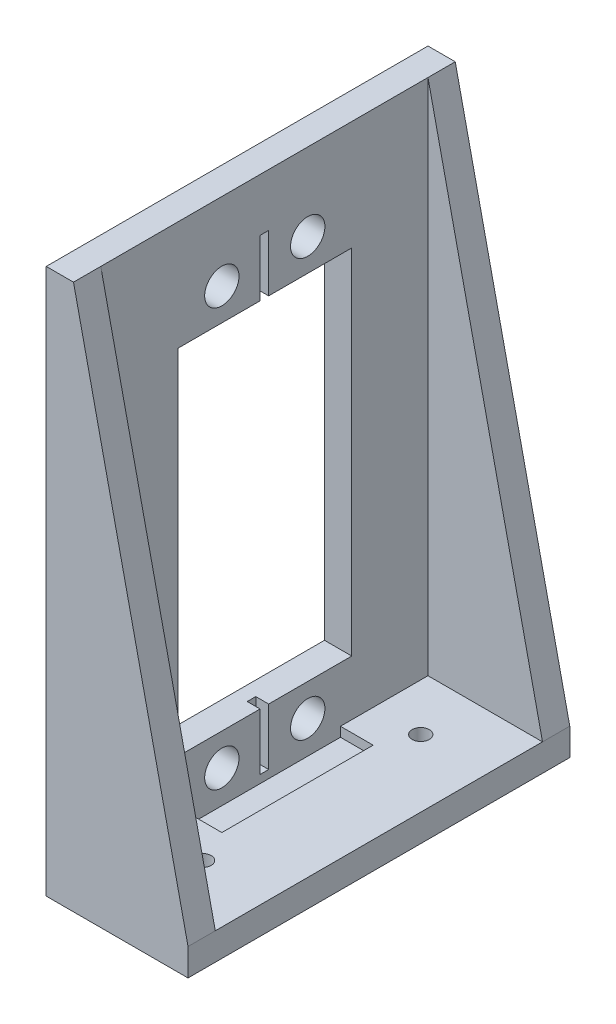
SolidWorks part; units mm, degrees
ref_plane "Front Plane" through (0, 0, 0) normal (0, 0, 1) x (1, 0, 0)
ref_plane "Top Plane" through (0, 0, 0) normal (0, 1, 0) x (1, 0, 0)
ref_plane "Right Plane" through (0, 0, 0) normal (1, 0, 0) x (0, 0, -1)
sketch "Sketch1" plane through (0, 0, 0) normal (0, 0, 1) x (1, 0, 0)
  line L0 (0, 0) -> (0, 63.5)
  line L1 (0, 63.5) -> (3.175, 63.5)
  line L2 (3.175, 63.5) -> (3.175, 3.175)
  line L3 (3.175, 3.175) -> (16.51, 3.175)
  line L4 (16.51, 3.175) -> (16.51, 0)
  line L5 (16.51, 0) -> (0, 0)
  dimension "D1" = 3.175
  dimension "D2" = 3.175
  dimension "D3" = 16.51
  dimension "D4" = 63.5
extrude "Boss-Extrude1" add sketch "Sketch1" along normal mid plane 44.45
sketch "Sketch3" plane through (0, 0, 22.225) normal (0, 0, 1) x (1, 0, 0)
  line L0 (3.175, 63.5) -> (16.51, 3.175)
  line L1 (16.51, 3.175) -> (3.175, 3.175)
  line L2 (3.175, 3.175) -> (3.175, 63.5)
extrude "Boss-Extrude2" add sketch "Sketch3" against normal blind 3.175
mirror "Mirror1" about plane through (0, 0, 0) normal (0, 0, 1) of "Boss-Extrude2"
sketch "Sketch4" plane through (0, 3.175, 0) normal (0, 1, 0) x (1, 0, 0)
  line L1 (3.175, 19.05) -> (16.51, 19.05) construction
  line L3 (3.175, 0) -> (16.51, 0) construction
  line L4 (3.175, -19.05) -> (3.175, 19.05) construction
  line L5 (16.51, -19.05) -> (16.51, 19.05) construction
  circle A0 centre (8.68, 12.7) radius 1
  circle A3 centre (8.68, -12.7) radius 1
  dimension "D1" = 2
  dimension "D2" = 6.35
  dimension "D3" = 5.505
extrude "Cut-Extrude2" cut sketch "Sketch4" against normal through all
sketch "Sketch5" plane through (3.175, 0, 0) normal (1, 0, 0) x (0, 0, -1)
  line L0 (-19.05, 63.5) -> (-19.05, 3.175) construction
  line L1 (-19.05, 3.175) -> (19.05, 3.175) construction
  circle A0 centre (-4.953, 5.875) radius 2
  circle A1 centre (5.047, 5.875) radius 2
  circle A2 centre (-4.953, 54.475) radius 2
  circle A3 centre (5.047, 54.475) radius 2
  dimension "D3" = 4
  dimension "D5" = 4
  dimension "D7" = 4
  dimension "D8" = 4
  dimension "D1" = 14.097
  dimension "D2" = 2.7
  dimension "D4" = 10
  dimension "D6" = 48.6
extrude "Cut-Extrude3" cut sketch "Sketch5" against normal through all
sketch "Sketch6" plane through (3.175, 0, 0) normal (1, 0, 0) x (0, 0, -1)
  line L0 (-10.08, 50.752) -> (10.174, 9.598) construction
  line L1 (-10.08, 50.752) -> (10.174, 50.752)
  line L2 (-10.08, 50.752) -> (-10.08, 9.598)
  line L3 (-10.08, 9.598) -> (10.174, 9.598)
  line L4 (10.174, 50.752) -> (10.174, 9.598)
  line L5 (10.174, 50.752) -> (-10.08, 9.598) construction
  line L6 (-4.953, 54.475) -> (5.047, 5.875) construction
  line L7 (-4.953, 5.875) -> (5.047, 54.475) construction
  point P12 (0.047, 30.175)
  point P13 (0.047, 30.175)
  dimension "D1" = 41.154
  dimension "D2" = 20.254
extrude "Cut-Extrude4" cut sketch "Sketch6" against normal through all
sketch "Sketch7" plane through (0, 50.752, 0) normal (0, -1, 0) x (1, 0, 0)
  line L0 (3.175, -10.174) -> (3.175, 10.08) construction
  line L1 (1.675, -0.5) -> (3.175, -0.5)
  line L2 (1.675, -0.5) -> (1.675, 0.5)
  line L3 (1.675, 0.5) -> (3.175, 0.5)
  line L4 (3.175, -0.5) -> (3.175, 0.5)
  line L5 (1.675, -0.5) -> (3.175, 0.5) construction
  line L6 (1.675, 0.5) -> (3.175, -0.5) construction
  line L7 (9.0805, 0) -> (-9.0805, 0) construction
  point P0 (2.425, 0)
  dimension "D1" = 1
  dimension "D2" = 1.5
extrude "Cut-Extrude5" cut sketch "Sketch7" against normal blind 6.604
extrude "Cut-Extrude6" cut sketch "Sketch7<2>" along normal blind 6.604 from surface starting at face at (1.5875, 9.598, -0.047)
sketch "Sketch7<2>" plane through (0, 50.752, 0) normal (0, -1, 0) x (1, 0, 0) same geometry as "Sketch7"
sketch "Sketch9" plane through (16.51, 0, 0) normal (1, 0, 0) x (0, 0, -1)
  line L1 (-8.763, 5.292) -> (8.857, 5.292)
  line L2 (-8.763, 5.292) -> (-8.763, 2.065)
  line L3 (-8.763, 2.065) -> (8.857, 2.065)
  line L4 (8.857, 5.292) -> (8.857, 2.065)
  circle A0 centre (5.047, 5.875) radius 2 construction
  circle A1 centre (-4.953, 5.875) radius 2 construction
  dimension "D1" = 3.81
  dimension "D2" = 3.81
  dimension "D3" = 3.81
extrude "Cut-Extrude7" cut sketch "Sketch9" along normal blind 3.81 from surface starting at face at (3.175, 30.9882, -0.0118)
equation "\"D1@Sketch4\"=2mm"
equation "\"tightTol\" = 0.005in"
equation "\"normTol\"= 0.01in"
equation "\"looseTol\"= 0.02in"
equation "\"D2@Sketch5\"=2.7mm"
equation "\"D3@Sketch5\"=4mm"
equation "\"D4@Sketch5\"=10mm"
equation "\"D5@Sketch5\"=4mm"
equation "\"D6@Sketch5\"=48.6mm"
equation "\"D8@Sketch5\"=4mm"
equation "\"D1@Sketch6\" = 40.9mm + \"normTol\""
equation "\"D2@Sketch6\" = 20mm + \"normTol\""
equation "\"D1@Sketch7\"=1mm"
equation "\"D2@Sketch7\"=1.5mm"
equation "\"D7@Sketch5\"=4mm"
equation "\"D3@Sketch4\"=0.125000in+2.33mm"
